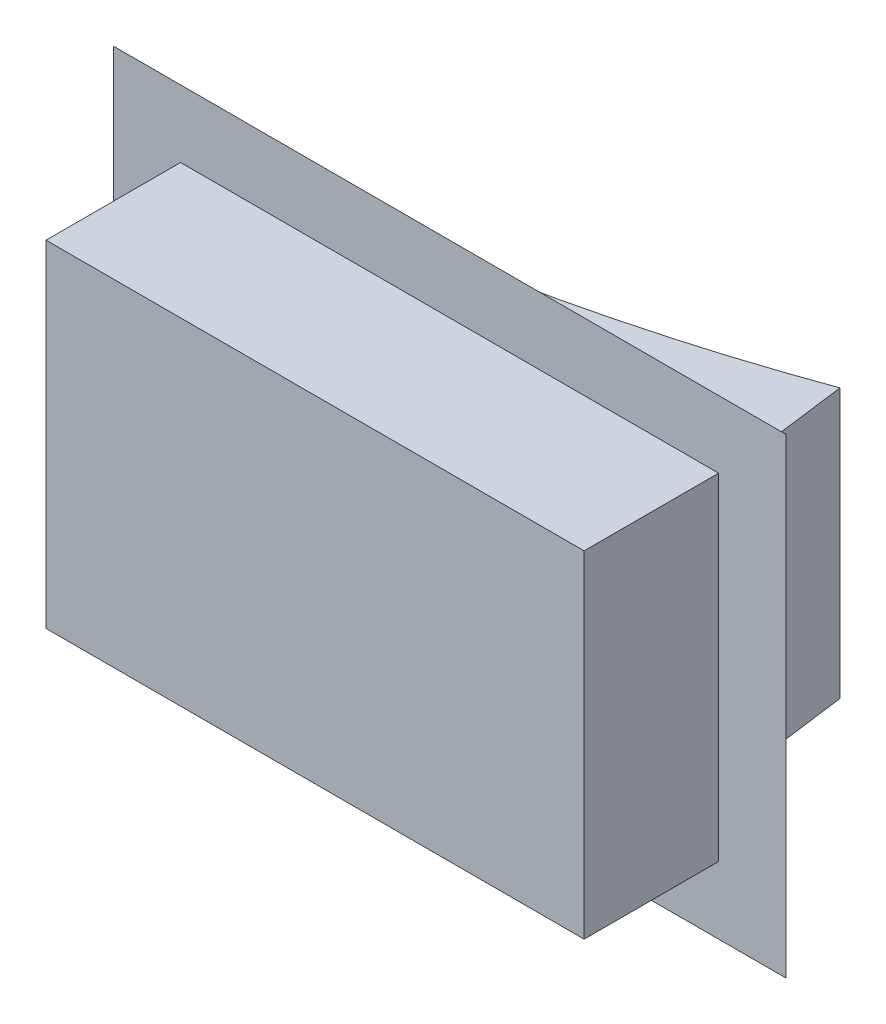
SolidWorks part; units mm, degrees
ref_plane "Front Plane" through (0, 0, 0) normal (0, 0, 1) x (1, 0, 0)
ref_plane "Top Plane" through (0, 0, 0) normal (0, 1, 0) x (1, 0, 0)
ref_plane "Right Plane" through (0, 0, 0) normal (1, 0, 0) x (0, 0, -1)
sketch "Sketch1" plane through (0, 0, 0) normal (0, 0, 1) x (1, 0, 0)
  line L1 (-10, 7) -> (10, 7)
  line L2 (-10, 7) -> (-10, -7)
  line L3 (-10, -7) -> (10, -7)
  line L4 (10, 7) -> (10, -7)
  point P4 (0, -7)
  point P5 (10, 0)
  dimension "D1" = 14
  dimension "D2" = 20
extrude "Boss-Extrude1" add sketch "Sketch1" along normal blind 2
chamfer "Chamfer3" distance 2 angle 45 4 edges at (-10, 0, 0) (0, -7, 0) (0, 7, 0) (10, 0, 0)
sketch "Sketch2" plane through (0, 0, 0) normal (0, 0, -1) x (-1, 0, 0)
  line L0 (8, 5) -> (-8, 5) construction
  line L1 (-7, -4) -> (7, -4)
  line L2 (-7, -4) -> (-7, 4)
  line L3 (-7, 4) -> (7, 4)
  line L4 (7, -4) -> (7, 4)
  line L5 (-8, -5) -> (8, -5) construction
  line L6 (-8, 5) -> (-8, -5) construction
  line L7 (8, -5) -> (8, 5) construction
  dimension "D1" = 1
  dimension "D2" = 1
  dimension "D3" = 1
  dimension "D4" = 1
extrude "Boss-Extrude2" add sketch "Sketch2" along normal blind 3
sketch "Sketch3" plane through (0, 4, 0) normal (0, 1, 0) x (1, 0, 0)
  line L0 (7, 0) -> (6.608, 3)
  line L1 (-7, 3) -> (7, 3) construction
  line L2 (7, 0) -> (-7, 0)
  line L3 (7, 3) -> (-7, 3)
  line L4 (-7, 3) -> (-7, 0)
  line L5 (6.608, 3) -> (7, 3)
  line L6 (7, 0) -> (7, 3)
  spline S0 degree 2 poles (6.608, 3) (-0.0193, 0.5805) (-7, 0) knots 0 0 0 1 1 1
  line M6 (7, 0) -> (7, 3)
  line M7 (7, 3) -> (-7, 3)
  line M8 (-7, 3) -> (-7, 0)
  dimension "D2" = 13.9765
  dimension "D1" = 3
  dimension "D3" = 13.608
  dimension "D4" = 9.478
extrude "Cut-Extrude1" cut sketch "Sketch3" against normal through all contours S0 M7 M8 | L0 M6 M7 region at (6.8693, 4, -2) region at (-2.0596, 4, -1.8799)
sketch "Sketch5" plane through (0, 0, 2) normal (0, 0, 1) x (1, 0, 0)
  line L0 (10, -7) -> (10, 7) construction
  line L1 (-8, 5) -> (8, 5)
  line L2 (-8, 5) -> (-8, -5)
  line L3 (-8, -5) -> (8, -5)
  line L4 (8, 5) -> (8, -5)
  line L5 (-10, 7) -> (-10, -7) construction
  line L6 (10, 7) -> (-10, 7) construction
  line L7 (-10, -7) -> (10, -7) construction
  dimension "D1" = 2
  dimension "D2" = 2
  dimension "D3" = 2
  dimension "D4" = 2
extrude "Boss-Extrude3" add sketch "Sketch5" along normal blind 4
ref_plane "Plane1" through (6.608, -4, -3) normal (-0.1296, 0, -0.9916) x (-0.9916, 0, 0.1296)
sketch "Sketch6" plane through (6.608, -4, -3) normal (-0.1296, 0, -0.9916) x (-0.9916, 0, 0.1296)
  line L0 (0, 0) -> (0, 4) construction
  line L1 (0, 8) -> (0, 0) construction
  line L2 (0, 4) -> (13.7863, 4) construction
  line L4 (12.1551, 4.15) -> (7.8959, 4.15)
  line L5 (12.1551, 4.15) -> (12.1551, 3.85)
  line L6 (12.1551, 3.85) -> (7.8959, 3.85)
  line L7 (7.8959, 4.15) -> (7.8959, 3.85)
  line L8 (12.1551, 4.15) -> (7.8959, 3.85) construction
  line L9 (12.1551, 3.85) -> (7.8959, 4.15) construction
  circle A0 centre (3.0929, 4) radius 1.8179
  circle A1 centre (3.0929, 4) radius 2.0179
  point P12 (10.0255, 4)
  dimension "D2" = 0.3
  dimension "D1" = 0.2
extrude "Cut-Extrude2" cut sketch "Sketch6" against normal blind 1.5
